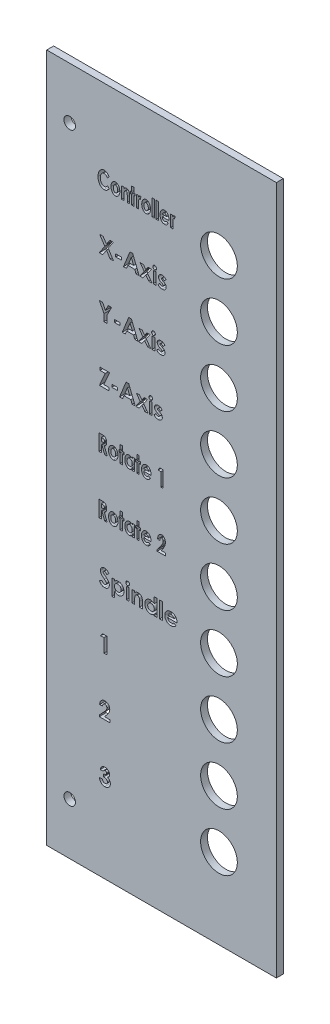
SolidWorks part; units mm, degrees
ref_plane "Front Plane" through (0, 0, 0) normal (0, 0, 1) x (1, 0, 0)
ref_plane "Top Plane" through (0, 0, 0) normal (0, 1, 0) x (1, 0, 0)
ref_plane "Right Plane" through (0, 0, 0) normal (1, 0, 0) x (0, 0, -1)
sketch "Sketch1" plane through (0, 0, 0) normal (0, 0, 1) x (1, 0, 0)
  line L1 (-50, -150) -> (50, -150)
  line L2 (-50, -150) -> (-50, 150)
  line L3 (-50, 150) -> (50, 150)
  line L4 (50, -150) -> (50, 150)
  point P4 (0, 150)
  point P6 (50, 0)
  dimension "D1" = 100
  dimension "D2" = 300
extrude "Boss-Extrude1" add sketch "Sketch1" along normal blind 3
sketch "Sketch2" plane through (0, 0, 3) normal (0, 0, 1) x (1, 0, 0)
  line L0 (25, -1000) -> (25, 49000) construction
  line L1 (50, 150) -> (-50, 150) construction
  line L2 (50, -150) -> (50, 150) construction
  line L3 (-30, 110) -> (25, 110) construction
  line L4 (-30, -40) -> (25, -40) construction
  line L5 (-30, 85) -> (25, 85) construction
  line L6 (-30, 60) -> (25, 60) construction
  line L7 (-30, 35) -> (25, 35) construction
  line L8 (-30, 10) -> (25, 10) construction
  line L9 (-30, -15) -> (25, -15) construction
  line L10 (-50, 150) -> (-50, -150) construction
  line L11 (-30, -65) -> (25, -65) construction
  line L12 (-30, -90) -> (25, -90) construction
  line L13 (-30, -115) -> (25, -115) construction
  circle A0 centre (25, 110) radius 8
  circle A2 centre (25, 85) radius 8
  circle A3 centre (25, 60) radius 8
  circle A4 centre (25, 35) radius 8
  circle A5 centre (25, 10) radius 8
  circle A6 centre (25, -15) radius 8
  circle A7 centre (25, -40) radius 8
  circle A8 centre (25, -65) radius 8
  circle A9 centre (25, -90) radius 8
  circle A10 centre (25, -115) radius 8
  text T0 "<b> Controller</b>" font "Century Gothic" height 7
  text T1 "<b> X-Axis</b>" font "Century Gothic" height 7
  text T2 "<b> Y-Axis</b>" font "Century Gothic" height 7
  text T3 "<b> Z-Axis</b>" font "Century Gothic" height 7
  text T4 "<b> Rotate 1</b>" font "Century Gothic" height 7
  text T5 "<b> Rotate 2</b>" font "Century Gothic" height 7
  text T6 "<b> Spindle</b>" font "Century Gothic" height 7
  text T7 "<b> 1</b>" font "Century Gothic" height 7
  text T8 " <b>2</b>" font "Century Gothic" height 7
  text T9 " <b>3</b>" font "Century Gothic" height 7
  dimension "D1" = 16
  dimension "D2" = 40
  dimension "D4" = 25
  dimension "D6" = 20
  dimension "D7" = 25
  dimension "D8" = 25
  dimension "D3" = 10
  dimension "D5" = 10
extrude "Cut-Extrude1" cut sketch "Sketch2" against normal through all
sketch "Sketch3" plane through (0, 0, 0) normal (0, 0, -1) x (-1, 0, 0)
  line L0 (-1000, 0) -> (49000, 0) construction
  line L1 (-50, 150) -> (50, 150) construction
  line L2 (50, 150) -> (50, -150) construction
  circle A0 centre (40, 127.5) radius 2.5
  circle A1 centre (40, -127.5) radius 2.5
  dimension "D2" = 10
  dimension "D3" = 5
  dimension "D1" = 22.5
extrude "Cut-Extrude4" cut sketch "Sketch3" against normal blind 3 contours A1 | A0 region at (-40, 127.5, 0) region at (-40, -127.5, 0)
